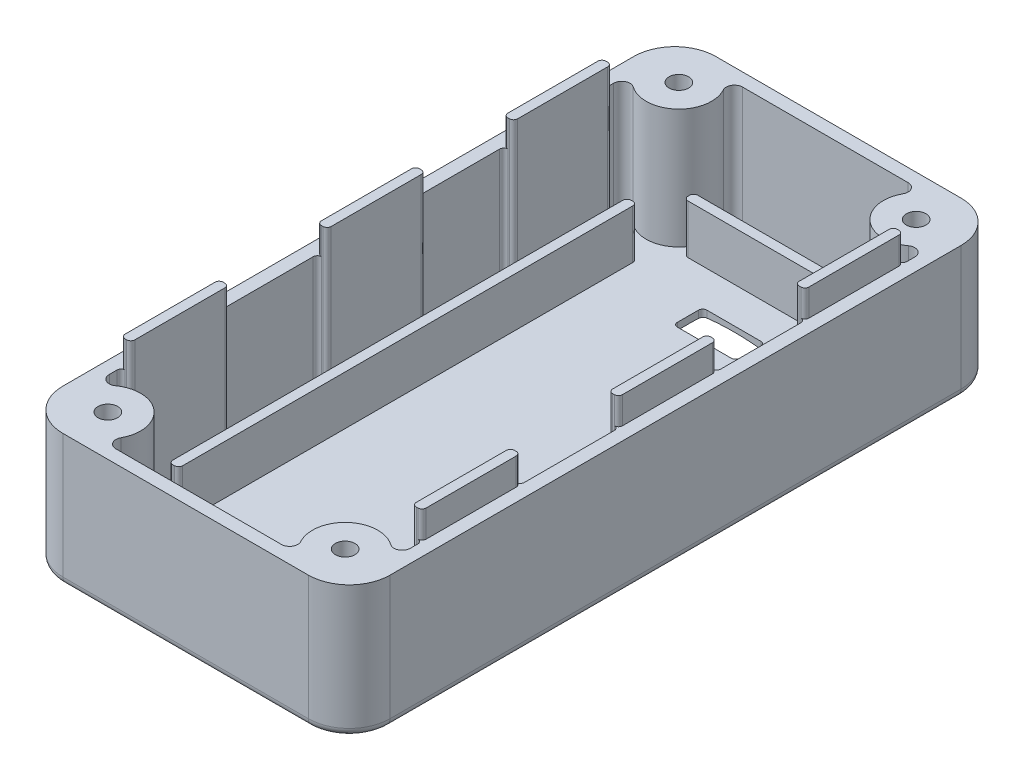
SolidWorks part; units mm, degrees
ref_plane "Front Plane" through (0, 0, 0) normal (0, 0, 1) x (1, 0, 0)
ref_plane "Top Plane" through (0, 0, 0) normal (0, 1, 0) x (1, 0, 0)
ref_plane "Right Plane" through (0, 0, 0) normal (1, 0, 0) x (0, 0, -1)
sketch "Base Sketch" plane through (0, 0, 0) normal (0, 1, 0) x (1, 0, 0)
  line L1 (0, 0) -> (40, 0)
  line L2 (0, 0) -> (0, 79.79)
  line L3 (0, 79.79) -> (40, 79.79)
  line L4 (40, 0) -> (40, 79.79)
extrude "Base" add sketch "Base Sketch" along normal blind 16.2
fillet "Corner Rounds R5" radius 5 4 edges at (0, 8.1, -79.79) (40, 8.1, -79.79) (40, 8.1, 0) (0, 8.1, 0)
shell "Shell" thickness 1.6 removed face at (20, 16.2, -39.895)
sketch "Sketch2" plane through (0, 0, 0) normal (0, 1, 0) x (1, 0, 0)
  circle A0 centre (5.5, 5) radius 4
  circle A1 centre (34.5, 5) radius 4
  circle A2 centre (5.5, 74.79) radius 4
  circle A3 centre (34.5, 74.79) radius 4
extrude "Screw Bosses" add sketch "Sketch2" along normal blind 16.2
sketch "Sketch3" plane through (0, 0, 0) normal (0, 1, 0) x (1, 0, 0)
  line L1 (1.6, 10.5) -> (2.8, 10.5)
  line L2 (1.6, 10.5) -> (1.6, 22.5)
  line L3 (1.6, 22.5) -> (2.8, 22.5)
  line L4 (2.8, 10.5) -> (2.8, 22.5)
  line L6 (1.6, 34.5) -> (2.8, 34.5)
  line L7 (1.6, 34.5) -> (1.6, 46.5)
  line L8 (1.6, 46.5) -> (2.8, 46.5)
  line L9 (2.8, 34.5) -> (2.8, 46.5)
  line L11 (1.6, 57.29) -> (2.8, 57.29)
  line L12 (1.6, 57.29) -> (1.6, 69.29)
  line L13 (1.6, 69.29) -> (2.8, 69.29)
  line L14 (2.8, 57.29) -> (2.8, 69.29)
  line L16 (37.2, 10.5) -> (38.4, 10.5)
  line L17 (37.2, 10.5) -> (37.2, 22.5)
  line L18 (37.2, 22.5) -> (38.4, 22.5)
  line L19 (38.4, 10.5) -> (38.4, 22.5)
  line L21 (37.2, 34.5) -> (38.4, 34.5)
  line L22 (37.2, 34.5) -> (37.2, 46.5)
  line L23 (37.2, 46.5) -> (38.4, 46.5)
  line L24 (38.4, 34.5) -> (38.4, 46.5)
  line L26 (37.2, 57.29) -> (38.4, 57.29)
  line L27 (37.2, 57.29) -> (37.2, 69.29)
  line L28 (37.2, 69.29) -> (38.4, 69.29)
  line L29 (38.4, 57.29) -> (38.4, 69.29)
extrude "Alignment Tabs" add sketch "Sketch3" along normal blind 19.5
fillet "Bottom Edge Round R1" radius 1 8 edges at (1.4645, 0, -1.4645) (20, 0, 0) (38.5355, 0, -1.4645) (40, 0, -39.895) (38.5355, 0, -78.3255) (20, 0, -79.79) (1.4645, 0, -78.3255) (0, 0, -39.895)
sketch "Sketch4" plane through (0, 0, 0) normal (0, 1, 0) x (1, 0, 0)
  circle A0 centre (5.5, 5) radius 1.2
  circle A1 centre (34.5, 5) radius 1.2
  circle A2 centre (5.5, 74.79) radius 1.2
  circle A3 centre (34.5, 74.79) radius 1.2
extrude "M2 Clearance Holes" cut sketch "Sketch4" along normal through all
sketch "Sketch5" plane through (0, 0, 0) normal (0, 1, 0) x (1, 0, 0)
  circle A0 centre (5.5, 5) radius 2.2
  circle A1 centre (34.5, 5) radius 2.2
  circle A2 centre (5.5, 74.79) radius 2.2
  circle A3 centre (34.5, 74.79) radius 2.2
extrude "M2 Counterbores" cut sketch "Sketch5" along normal blind 12.2
sketch "Slide Switch Cutout Sketch" plane through (0, 0, 0) normal (0, 1, 0) x (1, 0, 0)
  line L0 (16.2, 63.4) -> (23.8, 63.4)
  line L1 (23.8, 63.4) -> (23.8, 67)
  line L2 (23.8, 67) -> (16.2, 67)
  line L3 (16.2, 67) -> (16.2, 63.4)
extrude "Slide Switch Cutout" cut sketch "Slide Switch Cutout Sketch" along normal blind 2
sketch "2xAAA Guide Rails Sketch" plane through (0, 0, 0) normal (0, 1, 0) x (1, 0, 0)
  line L0 (32.85, 12) -> (34.05, 12)
  line L1 (34.05, 12) -> (34.05, 68)
  line L2 (34.05, 68) -> (32.85, 68)
  line L3 (32.85, 68) -> (32.85, 12)
  line L4 (5.95, 12) -> (7.15, 12)
  line L5 (7.15, 12) -> (7.15, 68)
  line L6 (7.15, 68) -> (5.95, 68)
  line L7 (5.95, 68) -> (5.95, 12)
extrude "2xAAA Guide Rails" add sketch "2xAAA Guide Rails Sketch" along normal blind 7.6
sketch "2xAAA End Rails Sketch" plane through (0, 0, 0) normal (0, 1, 0) x (1, 0, 0)
  line L0 (9.5, 7.2) -> (30.5, 7.2)
  line L1 (30.5, 7.2) -> (30.5, 8.4)
  line L2 (30.5, 8.4) -> (9.5, 8.4)
  line L3 (9.5, 8.4) -> (9.5, 7.2)
  line L4 (9.5, 71.4) -> (30.5, 71.4)
  line L5 (30.5, 71.4) -> (30.5, 72.6)
  line L6 (30.5, 72.6) -> (9.5, 72.6)
  line L7 (9.5, 72.6) -> (9.5, 71.4)
extrude "2xAAA End Rails" add sketch "2xAAA End Rails Sketch" along normal blind 7.6
chamfer "Rail Buttress Chamfers 3x45" distance 3 angle 45 4 edges at (20, 1.6, -72.6) (20, 1.6, -7.2) (5.95, 1.6, -40) (34.05, 1.6, -40) tangent propagation no
fillet "Lug Junction Fillets R1" radius 1 8 edges at (32.3929, 8.9, -78.19) (38.4, 8.9, -73.9012) (7.6071, 8.9, -78.19) (1.6, 8.9, -73.9012) (32.3929, 8.9, -1.6) (38.4, 8.9, -5.8888) (7.6071, 8.9, -1.6) (1.6, 8.9, -5.8888)
ref_plane "Switch Dish Plane X20" through (20, 0, 0) normal (1, 0, 0) x (0, 0, -1)
sketch "Switch Dish Sketch" plane through (20, 0, 0) normal (1, 0, 0) x (0, 0, -1)
  line L0 (65.2, -1) -> (65.2, 2) construction
  line L1 (72.7, 0) -> (72.7, -0.5)
  line L2 (72.7, -0.5) -> (65.2, -0.5)
  line L3 (65.2, -0.5) -> (65.2, 1)
  arc A0 (65.2, 1) -> (72.7, 0) centre (65.2, -27.625) cw
revolve "Switch Finger Dish D15x1" cut sketch "Switch Dish Sketch" angle 360 about L0
chamfer "Chamfer2" distance 1 angle 45 3 edges at (5.5, 12.2, -2.8) (34.5, 12.2, -2.8) (34.5, 12.2, -72.59)
fillet "Fillet2" radius 0.5 44 edges at (37.2, 10.55, -69.29) (38.4, 8.9, -69.29) (32.85, 4.6, -68) (32.85, 4.6, -12) (30.5, 4.6, -71.4) (30.5, 4.6, -8.4) (9.5, 4.6, -71.4) (9.5, 4.6, -8.4) (7.15, 4.6, -68) (7.15, 4.6, -12) (34.05, 6.1, -68) (34.05, 6.1, -12) (30.5, 6.1, -72.6) (30.5, 6.1, -7.2) (9.5, 6.1, -72.6) (9.5, 6.1, -7.2) (5.95, 6.1, -68) (5.95, 6.1, -12) (23.8, 1.1447, -67) (23.8, 1.1447, -63.4) (16.2, 1.1447, -67) (16.2, 1.1447, -63.4) (37.2, 10.55, -57.29) (37.2, 10.55, -46.5) (37.2, 10.55, -34.5) (37.2, 10.55, -22.5) (37.2, 10.55, -10.5) (2.8, 10.55, -69.29) (2.8, 10.55, -57.29) (2.8, 10.55, -46.5) (2.8, 10.55, -34.5) (2.8, 10.55, -22.5) (2.8, 10.55, -10.5) (38.4, 8.9, -57.29) (38.4, 8.9, -46.5) (38.4, 8.9, -34.5) (38.4, 8.9, -22.5) (38.4, 8.9, -10.5) (1.6, 8.9, -69.29) (1.6, 8.9, -57.29) (1.6, 8.9, -46.5) (1.6, 8.9, -34.5) (1.6, 8.9, -22.5) (1.6, 8.9, -10.5)
fillet "Tab Top Corner Fillets R0.5" radius 0.5 12 edges at (38.4, 17.85, -57.29) (38.4, 17.85, -69.29) (38.4, 17.85, -34.5) (38.4, 17.85, -46.5) (38.4, 17.85, -10.5) (38.4, 17.85, -22.5) (1.6, 17.85, -57.29) (1.6, 17.85, -69.29) (1.6, 17.85, -34.5) (1.6, 17.85, -46.5) (1.6, 17.85, -22.5) (1.6, 17.85, -10.5)
